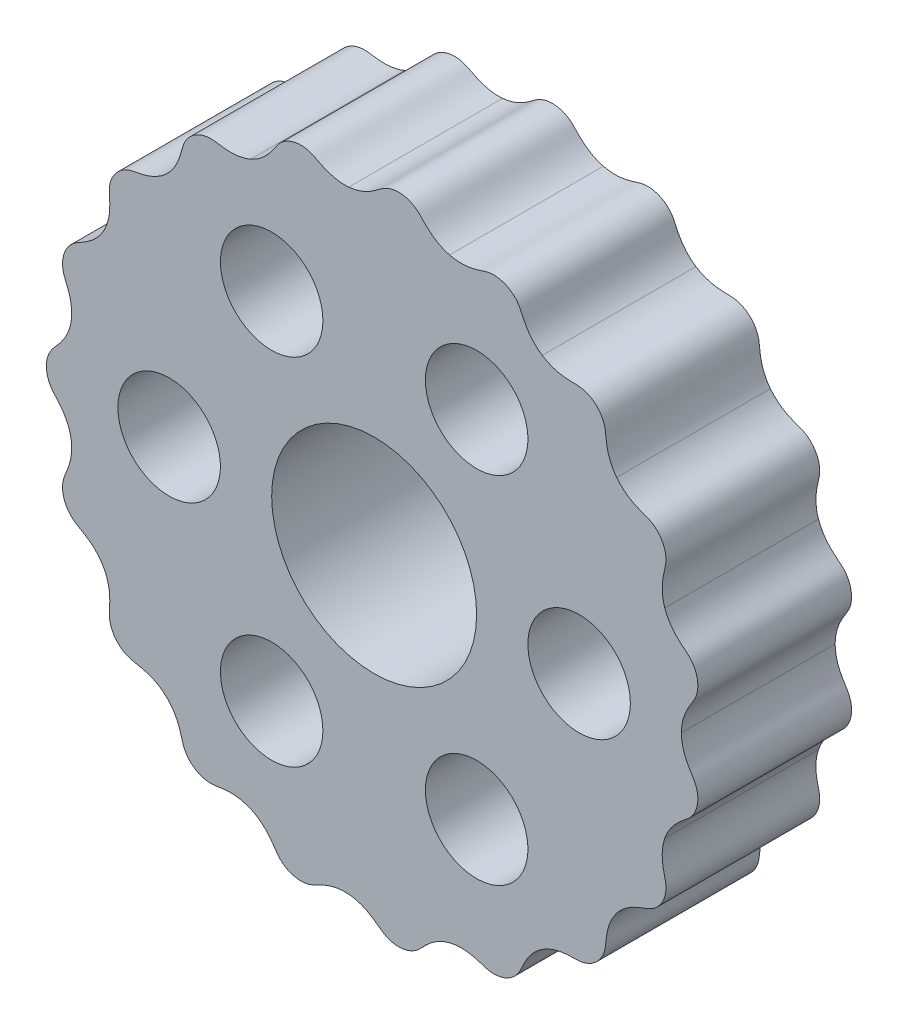
SolidWorks part; units mm, degrees
note: The reader was unsure of these and kept them because the rebuilt part matched: shared geometry of "driver<3>".
material "Stop 1060"
ref_plane "Płaszczyzna przednia" through (0, 0, 0) normal (0, 0, 1) x (1, 0, 0)
ref_plane "Płaszczyzna górna" through (0, 0, 0) normal (0, 1, 0) x (1, 0, 0)
ref_plane "Płaszczyzna prawa" through (0, 0, 0) normal (1, 0, 0) x (0, 0, -1)
sketch "driver" plane through (0, 0, 0) normal (0, 0, 1) x (1, 0, 0)
  line L0 (1029.98, 1000) -> (1028.3556, 990.2655)
  circle A0 centre (1000, 1000) radius 10
  circle A1 centre (1000, 1000) radius 29.98
  spline S0 degree 3 poles (1030.1925, 1001.3933) (1030.0526, 1000.9432) (1029.9418, 1000.2228) (1030.0182, 999.2795) (1030.1688, 998.6408) (1030.3604, 998.1257) (1030.5494, 997.7322) (1030.7144, 997.4364) (1030.8507, 997.2112) (1030.9616, 997.0341) (1031.0527, 996.8887) (1031.1292, 996.7631) (1031.1954, 996.6491) (1031.2544, 996.5408) (1031.308, 996.4339) (1031.3573, 996.3255) (1031.4028, 996.2135) (1031.4445, 996.0966) (1031.482, 995.9739) (1031.5147, 995.8451) (1031.542, 995.7104) (1031.5632, 995.5699) (1031.5775, 995.4246) (1031.5845, 995.2751) (1031.5836, 995.1226) (1031.5745, 994.9682) (1031.557, 994.8133) (1031.5313, 994.6591) (1031.4975, 994.5069) (1031.456, 994.358) (1031.4073, 994.2134) (1031.3522, 994.0743) (1031.2914, 993.9415) (1031.2258, 993.8155) (1031.1562, 993.6969) (1031.0835, 993.5858) (1031.0082, 993.4819) (1030.9308, 993.3848) (1030.8514, 993.2937) (1030.7695, 993.2072) (1030.6841, 993.1235) (1030.5932, 993.0402) (1030.4936, 992.9538) (1030.3804, 992.8599) (1030.2471, 992.7519) (1030.0847, 992.6205) (1029.8827, 992.4518) (1029.6305, 992.2256) (1029.324, 991.9148) (1028.9755, 991.4898) (1028.6257, 990.9346) (1028.2471, 990.0672) (1028.118, 989.3499) (1028.1041, 988.8787) knots 0 0 0 0 0.100714 0.15386 0.201428 0.240528 0.271124 0.294665 0.312906 0.327391 0.339321 0.349585 0.358826 0.367504 0.375946 0.384378 0.392955 0.401778 0.410907 0.420369 0.430169 0.440293 0.450712 0.461386 0.472266 0.483298 0.494422 0.505578 0.516702 0.527734 0.538614 0.549288 0.559707 0.569831 0.579631 0.589093 0.598222 0.607045 0.615622 0.624054 0.632496 0.641174 0.650415 0.660679 0.672609 0.687094 0.705335 0.728876 0.759472 0.798572 0.84614 0.899286 1 1 1 1
  point P0 (1030.1925, 1001.3933)
  point P1 (1030.0399, 1000.7434)
  point P2 (1029.98, 1000)
  point P3 (1030.0399, 999.2566)
  point P4 (1030.1925, 998.6067)
  point P5 (1030.3829, 998.0921)
  point P6 (1030.5681, 997.7047)
  point P7 (1030.7284, 997.4158)
  point P8 (1030.8605, 997.1965)
  point P9 (1030.968, 997.024)
  point P10 (1031.0565, 996.8819)
  point P11 (1031.1312, 996.7588)
  point P12 (1031.1962, 996.6465)
  point P13 (1031.2543, 996.5395)
  point P14 (1031.3073, 996.4335)
  point P15 (1031.3563, 996.3258)
  point P16 (1031.4016, 996.2143)
  point P17 (1031.4431, 996.0977)
  point P18 (1031.4806, 995.9751)
  point P19 (1031.5133, 995.8464)
  point P20 (1031.5406, 995.7117)
  point P21 (1031.5618, 995.5712)
  point P22 (1031.5762, 995.4257)
  point P23 (1031.5831, 995.276)
  point P24 (1031.5822, 995.1233)
  point P25 (1031.5731, 994.9688)
  point P26 (1031.5557, 994.8136)
  point P27 (1031.5299, 994.6592)
  point P28 (1031.4961, 994.5068)
  point P29 (1031.4545, 994.3577)
  point P30 (1031.4058, 994.213)
  point P31 (1031.3506, 994.0737)
  point P32 (1031.2897, 993.9408)
  point P33 (1031.2241, 993.8148)
  point P34 (1031.1545, 993.6962)
  point P35 (1031.0817, 993.5851)
  point P36 (1031.0066, 993.4813)
  point P37 (1030.9294, 993.3845)
  point P38 (1030.8503, 993.2937)
  point P39 (1030.769, 993.2077)
  point P40 (1030.6845, 993.1248)
  point P41 (1030.5948, 993.0424)
  point P42 (1030.4969, 992.9573)
  point P43 (1030.3862, 992.8651)
  point P44 (1030.2563, 992.7595)
  point P45 (1030.0986, 992.6312)
  point P46 (1029.9025, 992.4667)
  point P47 (1029.6571, 992.2455)
  point P48 (1029.3562, 991.9392)
  point P49 (1029.009, 991.5143)
  point P50 (1028.6536, 990.9492)
  point P51 (1028.3556, 990.2655)
  point P52 (1028.1708, 989.5429)
  point P53 (1028.1041, 988.8787)
  point P63 (999, 1000)
  dimension "D109" = 1000
  dimension "eccentrity_hole" = 20
  dimension "D1" = 1030.1925
  dimension "D2" = 1030.0399
  dimension "D3" = 1029.98
  dimension "D4" = 1030.0399
  dimension "D5" = 1030.1925
  dimension "D6" = 1030.3829
  dimension "D7" = 1030.5681
  dimension "D8" = 1030.7284
  dimension "D9" = 1030.8605
  dimension "D10" = 1030.968
  dimension "D11" = 1031.0565
  dimension "D12" = 1031.1312
  dimension "D13" = 1031.1962
  dimension "D14" = 1031.2543
  dimension "D15" = 1031.3073
  dimension "D16" = 1031.3563
  dimension "D17" = 1031.4016
  dimension "D18" = 1031.4431
  dimension "D19" = 1031.4806
  dimension "D20" = 1031.5133
  dimension "D21" = 1031.5406
  dimension "D22" = 1031.5618
  dimension "D23" = 1031.5762
  dimension "D24" = 1031.5831
  dimension "D25" = 1031.5822
  dimension "D26" = 1031.5731
  dimension "D27" = 1031.5557
  dimension "D28" = 1031.5299
  dimension "D29" = 1031.4961
  dimension "D30" = 1031.4545
  dimension "D31" = 1031.4058
  dimension "D32" = 1031.3506
  dimension "D33" = 1031.2897
  dimension "D34" = 1031.2241
  dimension "D35" = 1031.1545
  dimension "D36" = 1031.0817
  dimension "D37" = 1031.0066
  dimension "D38" = 1030.9294
  dimension "D39" = 1030.8503
  dimension "D40" = 1030.769
  dimension "D41" = 1030.6845
  dimension "D42" = 1030.5948
  dimension "D43" = 1030.4969
  dimension "D44" = 1030.3862
  dimension "D45" = 1030.2563
  dimension "D46" = 1030.0986
  dimension "D47" = 1029.9025
  dimension "D48" = 1029.6571
  dimension "D49" = 1029.3562
  dimension "D50" = 1029.009
  dimension "D51" = 1028.6536
  dimension "D52" = 1028.3556
  dimension "D53" = 1028.1708
  dimension "D54" = 1028.1041
  dimension "D55" = 1001.3933
  dimension "D56" = 1000.7434
  dimension "D57" = 1000
  dimension "D58" = 999.2566
  dimension "D59" = 998.6067
  dimension "D60" = 998.0921
  dimension "D61" = 997.7047
  dimension "D62" = 997.4158
  dimension "D63" = 997.1965
  dimension "D64" = 997.024
  dimension "D65" = 996.8819
  dimension "D66" = 996.7588
  dimension "D67" = 996.6465
  dimension "D68" = 996.5395
  dimension "D69" = 996.4335
  dimension "D70" = 996.3258
  dimension "D71" = 996.2143
  dimension "D72" = 996.0977
  dimension "D73" = 995.9751
  dimension "D74" = 995.8464
  dimension "D75" = 995.7117
  dimension "D76" = 995.5712
  dimension "D77" = 995.4257
  dimension "D78" = 995.276
  dimension "D79" = 995.1233
  dimension "D80" = 994.9688
  dimension "D81" = 994.8136
  dimension "D82" = 994.6592
  dimension "D83" = 994.5068
  dimension "D84" = 994.3577
  dimension "D85" = 994.213
  dimension "D86" = 994.0737
  dimension "D87" = 993.9408
  dimension "D88" = 993.8148
  dimension "D89" = 993.6962
  dimension "D90" = 993.5851
  dimension "D91" = 993.4813
  dimension "D92" = 993.3845
  dimension "D93" = 993.2937
  dimension "D94" = 993.2077
  dimension "D95" = 993.1248
  dimension "D96" = 993.0424
  dimension "D97" = 992.9573
  dimension "D98" = 992.8651
  dimension "D99" = 992.7595
  dimension "D100" = 992.6312
  dimension "D101" = 992.4667
  dimension "D102" = 992.2455
  dimension "D103" = 991.9392
  dimension "D104" = 991.5143
  dimension "D105" = 990.9492
  dimension "D106" = 990.2655
  dimension "D107" = 989.5429
  dimension "D108" = 988.8787
  dimension "D110" = 1000
  dimension "eccentrity" = 1
extrude "1" add sketch "driver" along normal mid plane 15 contours A1 A0 | L0 A1
extrude "2" add sketch "driver<3>" along normal up to surface and the other way up to surface contours S0 A1 | L0 A1 up to face at (1010, 1000, 7.5) other way up to face at (1010, 1000, -7.5)
sketch "driver<3>" plane through (0, 0, 0) normal (0, 0, 1) x (1, 0, 0) same geometry as "driver"
pattern_circular "3" count 19 over 360 about axis through (1000, 1000, 7.5) along (0, 0, -1) of "2"
sketch "4" plane through (0, 0, 7.5) normal (0, 0, 1) x (1, 0, 0)
  circle A0 centre (1020, 1000) radius 5
  circle A1 centre (1000, 1000) radius 10 construction
  point P5 (1000, 1000)
  dimension "D1" = 20
  dimension "D2" = 10
extrude "5" cut sketch "4" against normal through all
pattern_circular "6" count 6 over 360 about axis through (1000, 1000, 0) along (0, 0, 1) of "5"
sketch "ROLLERS" plane through (0, 0, 0) normal (0, 0, 1) x (1, 0, 0)
  circle A0 centre (1034, 1000) radius 4
  circle A1 centre (999, 1000) radius 35 construction
  circle A2 centre (1032.287, 989.1844) radius 4
  circle A3 centre (1027.3156, 979.4275) radius 4
  circle A4 centre (1019.5725, 971.6844) radius 4
  circle A5 centre (1009.8156, 966.713) radius 4
  circle A6 centre (999, 965) radius 4
  circle A7 centre (988.1844, 966.713) radius 4
  circle A8 centre (978.4275, 971.6844) radius 4
  circle A9 centre (970.6844, 979.4275) radius 4
  circle A10 centre (965.713, 989.1844) radius 4
  circle A11 centre (964, 1000) radius 4
  circle A12 centre (965.713, 1010.8156) radius 4
  circle A13 centre (970.6844, 1020.5725) radius 4
  circle A14 centre (978.4275, 1028.3156) radius 4
  circle A15 centre (988.1844, 1033.287) radius 4
  circle A16 centre (999, 1035) radius 4
  circle A17 centre (1009.8156, 1033.287) radius 4
  circle A18 centre (1019.5725, 1028.3156) radius 4
  circle A27 centre (1027.3156, 1020.5725) radius 4
  circle A28 centre (1032.287, 1010.8156) radius 4
  point P58 (999, 1000)
  dimension "Rr" = 4
  dimension "R" = 35
  dimension "N" = 20
sketch "INNER_SHAFTS" plane through (0, 0, 0) normal (0, 0, 1) x (1, 0, 0)
  circle A0 centre (999, 1000) radius 20 construction
  circle A1 centre (1019, 1000) radius 4
  circle A2 centre (1009, 982.6795) radius 4
  circle A3 centre (989, 982.6795) radius 4
  circle A4 centre (979, 1000) radius 4
  circle A5 centre (989, 1017.3205) radius 4
  circle A6 centre (1009, 1017.3205) radius 4
  point P18 (999, 1000)
  dimension "W" = 20
  dimension "WD" = 8
  dimension "L" = 6
